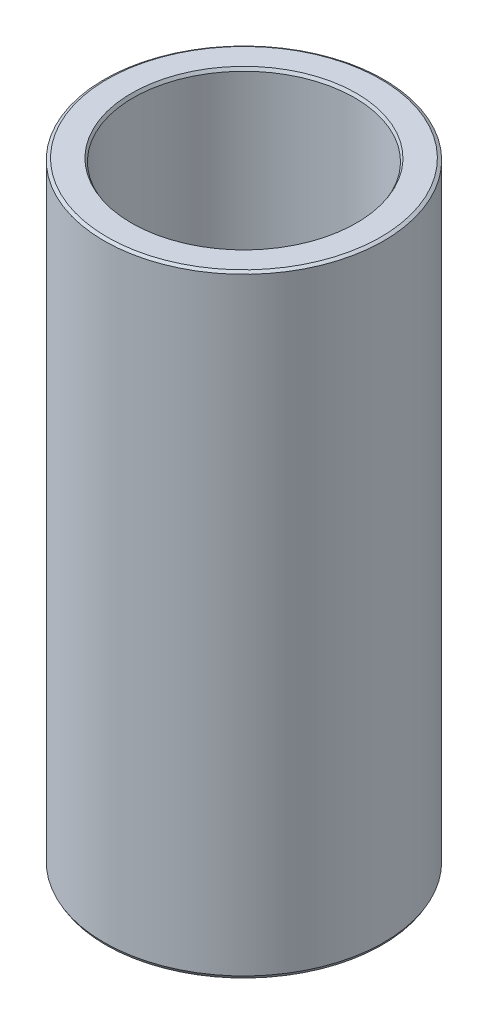
SolidWorks part; units mm, degrees
ref_plane "Front Plane" through (0, 0, 0) normal (0, 0, 1) x (1, 0, 0)
ref_plane "Top Plane" through (0, 0, 0) normal (0, 1, 0) x (1, 0, 0)
ref_plane "Right Plane" through (0, 0, 0) normal (1, 0, 0) x (0, 0, -1)
sketch "Sketch1" plane through (0, 0, 0) normal (0, 1, 0) x (1, 0, 0)
  circle A0 centre (0, 0) radius 50
  dimension "SLEEVE_OD" = 100
extrude "Boss-Extrude1" add sketch "Sketch1" along normal blind 219.0048
sketch "Sketch2" plane through (0, 0, 0) normal (0, 1, 0) x (1, 0, 0)
  circle A0 centre (0, 0) radius 39.5936
  dimension "BORE_D" = 79.1872
extrude "Cut-Extrude1" cut sketch "Sketch2" along normal through all
chamfer "Chamfer1" distance 0.6253 angle 60 4 edges at (0, 219.0048, 39.5936) (0, 0, 39.5936) (0, 0, 50) (0, 219.0048, 50) first distance on face at (0, 219.0048, 39.5936) first distance on face at (0, 0, 39.5936) first distance on face at (0, 219.0048, 50)
